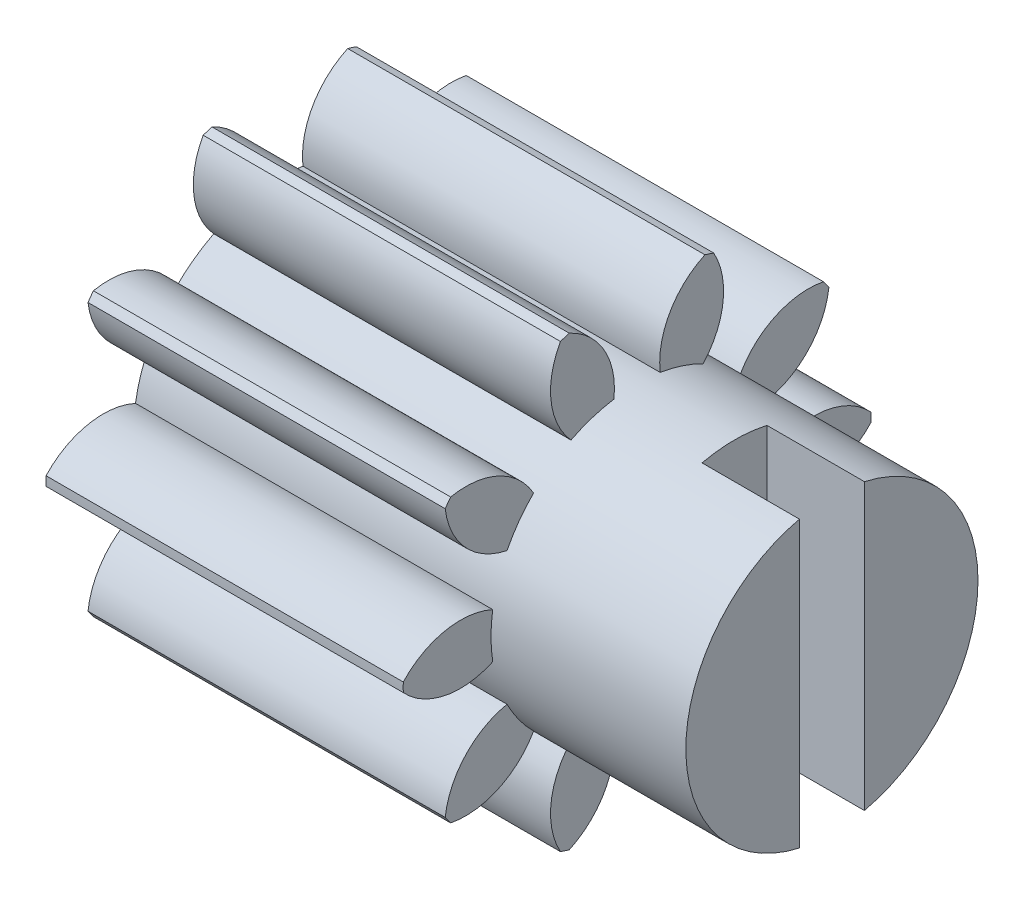
SolidWorks part; units mm, degrees
ref_plane "Plane1" through (0, 0, 0) normal (0, 0, 1) x (1, 0, 0)
ref_plane "Plane2" through (0, 0, 0) normal (0, 1, 0) x (1, 0, 0)
ref_plane "Plane3" through (0, 0, 0) normal (1, 0, 0) x (0, 0, -1)
other "Configuration Table"
sketch "HoldingSke" plane through (0, 0, 0) normal (0, 1, 0) x (1, 0, 0)
  line L0 (0, 0) -> (1.6413, -0.2894)
  line L1 (-15, 0) -> (100, 0) construction
  line L2 (0, 0) -> (-2.1039, 2.3779)
  line L3 (0, 0) -> (-11.863, 4.5341)
  line L4 (0, 0) -> (8.5048, 1.4996)
  line L5 (0, 0) -> (-46.8476, -17.4728)
  line L6 (0, 0) -> (-4.5593, -3.0762)
  line L7 (-2.1039, 2.3779) -> (8.6586, 51.2059)
  line L8 (-76.2, 54.61) -> (-76.1, 54.61)
  line L9 (-71.009, 38.7566) -> (-53.1078, 45.2721)
  line L10 (-76.2, 71.12) -> (104.1128, 71.12)
  line L11 (0, 0) -> (-5.5, 0)
  line L12 (-76.2, 101.6) -> (-76.177, 101.6)
  line L13 (24.9733, 27.94) -> (52.9518, 28.4284)
  line L14 (24.9733, 27.94) -> (24.9743, 27.94)
  line L15 (24.9733, 27.94) -> (100.4006, 29.5858)
  line L16 (-63.627, -0.6) -> (-12.827, -0.6)
  circle A0 centre (0, 0) radius 0.5
  circle A1 centre (0, 0) radius 2.249
  circle A2 centre (0, 0) radius 37.5
  circle A3 centre (0, 0) radius 0.5
  dimension "Num_teeth" = 10
  dimension "Pitch_radius" = 180.3128
  dimension "Width" = 5.5
  dimension "Thickness" = 5.5
sketch "BasProSke" plane through (0, 0, 0) normal (0, 1, 0) x (1, 0, 0)
  line L0 (-10, 0) -> (60, 0) construction
  line L1 (0, 0) -> (0, 3.6)
  line L2 (0, 0) -> (5.5, 0)
  line L3 (5.5, 0) -> (5.5, 3.6)
  line L4 (5.5, 3.6) -> (0, 3.6)
  dimension "Thickness" = 5.5
  dimension "Diameter" = 7.2
revolve "Base-Revolve" add sketch "BasProSke" angle 360 about L0
sketch "TooCutSke" plane through (0, 0, 0) normal (1, 0, 0) x (0, 0, -1)
  line L1 (0, 0) -> (0, 107) construction
  line L2 (0, 0) -> (-0.5095, 2.9564) construction
  line L3 (0, 0) -> (-1.835, 5.6477) construction
  line L4 (-0.5095, 2.9564) -> (-0.9175, 2.8238) construction
  arc A0 (0.356, 2.2206) -> (-0.356, 2.2206) centre (0, 0) ccw
  arc A1 (1.0802, 3.4607) -> (-1.0802, 3.4607) centre (0, 0) ccw
  circle A2 centre (0, 0) radius 3 construction
  circle A3 centre (0, 0) radius 2.8191 construction
  arc A4 (-0.356, 2.2206) -> (-1.0802, 3.4607) centre (-1.5483, 2.3558) ccw
  arc A5 (1.0802, 3.4607) -> (0.356, 2.2206) centre (1.5483, 2.3558) ccw
extrude "ToothCut" cut sketch "TooCutSke" along normal through all
fillet "Breaks" [suppressed] radius 0.012 tangent propagation no
fillet "RootFillets" [suppressed] radius 0.151
pattern_circular "TeethCuts" count 10 every 36 about axis through (-10, 0, 0) along (1, 0, 0) of "ToothCut", "RootFillets", "Breaks"
sketch "HubNeaOneSke" plane through (0, 0, 0) normal (-1, 0, 0) x (0, 0, 1)
  circle A0 centre (0, 0) radius 2.249
  dimension "Diameter" = 4.498
extrude "HubNearOne" [suppressed] add sketch "HubNeaOneSke" along normal blind 44.5001
sketch "HubNeaBotSke" plane through (0, 0, 0) normal (-1, 0, 0) x (0, 0, 1)
  circle A0 centre (0, 0) radius 2.249
  dimension "Diameter" = 4.498
extrude "HubNearBoth" [suppressed] add sketch "HubNeaBotSke" along normal blind 22.25
ref_plane "FarPln" through (5.5, 0, 0) normal (1, 0, 0) x (0, 0, -1)
sketch "HubFarSke" plane through (5.5, 0, 0) normal (1, 0, 0) x (0, 0, -1)
  circle A0 centre (0, 0) radius 2.249
  dimension "Diameter" = 4.498
extrude "HubFar" [suppressed] add sketch "HubFarSke" along normal blind 22.25
sketch "BorSke" plane through (0, 0, 0) normal (1, 0, 0) x (0, 0, -1)
  circle A0 centre (0, 0) radius 0.5
  dimension "Diameter" = 1
extrude "Bore" cut sketch "BorSke" along normal mid plane 100.0001
sketch "KeySke" plane through (0, 0, 0) normal (1, 0, 0) x (0, 0, -1)
  line L0 (-0.05, 0) -> (-0.05, 0.6)
  line L1 (-0.05, 0.6) -> (0.05, 0.6)
  line L2 (0.05, 0.6) -> (0.05, 0)
  line L3 (0, 0) -> (0, 34) construction
  line L4 (-0.05, 0) -> (0.05, 0)
  dimension "Width" = 0.1
extrude "Keyway" [suppressed] cut sketch "KeySke" along normal mid plane 100.0001
pattern_circular "Keyway2" [suppressed] count 2 every 90 about axis through (-10, 0, 0) along (1, 0, 0)
sketch "草图1" plane through (5.5, 0, 0) normal (1, 0, 0) x (0, 0, -1)
  circle A0 centre (0, 0) radius 0.5
  circle A1 centre (0, 0) radius 2.249
extrude "凸台-拉伸1" add sketch "草图1" along normal blind 3
sketch "草图2" plane through (8.5, 0, 0) normal (1, 0, 0) x (0, 0, -1)
  line L0 (-0.5, 0) -> (-0.5, -2.1927)
  line L1 (-0.5, 0) -> (-0.5, 2.1927)
  line L2 (0.5, 0) -> (0.5, 2.1927)
  line L3 (0.5, 0) -> (0.5, -2.1927)
  circle A0 centre (0, 0) radius 0.5 construction
  circle A1 centre (0, 0) radius 2.249 construction
  arc A2 (0.356, -2.2206) -> (1.0173, -2.0058) centre (0, 0) ccw construction
  arc A3 (-0.5, -2.1927) -> (0.5, -2.1927) centre (0, 0) ccw
  arc A5 (0.5, 2.1927) -> (-0.5, 2.1927) centre (0, 0) ccw
extrude "切除-拉伸1" cut sketch "草图2" against normal blind 1.5
equation "' \"Module@HoldingSke\" = 6.35"
equation "' \"Num_teeth@HoldingSke\" = 12"
equation "' \"Ap@HoldingSke\" =  20"
equation "' \"Ap@HoldingSke\" = 20"
equation "' \"Width@HoldingSke\" = 0.5 * 25.4"
equation "' \"Hub_dia@HoldingSke\"= 1 * 25.4"
equation "' \"Hub_dia@HoldingSke\" = 1 * 25.4"
equation "' \"Overall_len@HoldingSke\" = 1.0 * 25.4"
equation "' \"Bore@HoldingSke\" = 0.75 * 25.4"
equation "' \"T_dim@HoldingSke\" = 0.1 * 25.4"
equation "' \"Width@KeySke\" = 0.25 * 25.4"
equation "' \"Show_teeth@HoldingSke\" = 13"
equation "' \"Backlash@HoldingSke\" = 0.009 * 25.4"
equation "' \"Addendum_fac@HoldingSke\" = 1.0"
equation "' \"Dedendum_fac@HoldingSke\" = 1.25"
equation "' \"Dedendum_add@HoldingSke\" = 0.00005 * 25.4"
equation "' \"Clearance_fac@HoldingSke\" = 0.25"
equation "\"Pitch@HoldingSke\" = 1 / \"Module@HoldingSke\""
equation "\"Overcut_dia@TooCutSke\" = (\"Num_teeth@HoldingSke\" + 2 * \"Addendum_fac@HoldingSke\") / \"Pitch@HoldingSke\" + 0.002 * 25.4"
equation "\"Pitch_dia@TooCutSke\" = \"Num_teeth@HoldingSke\" / \"Pitch@HoldingSke\""
equation "\"Base_dia@TooCutSke\" = \"Num_teeth@HoldingSke\" / \"Pitch@HoldingSke\" * cos((\"Ap@HoldingSke\"  * 3.14159265 / 180))"
equation "\"Root_dia@TooCutSke\" = (\"Num_teeth@HoldingSke\" + 2) / \"Pitch@HoldingSke\" - 2 * (\"Addendum_fac@HoldingSke\" + \"Dedendum_fac@HoldingSke\") / \"Pitch@HoldingSke\" - \"Dedendum_add@HoldingSke\" * 2"
equation "\"Half_ang@TooCutSke\" = 180 / \"Num_teeth@HoldingSke\""
equation "\"Half_CT@TooCutSke\" = \"Num_teeth@HoldingSke\" / \"Pitch@HoldingSke\" * sin((3.14159265 / 2 / \"Num_teeth@HoldingSke\")) / 2 - 7 * \"Backlash@HoldingSke\" / 4"
equation "\"Flank_rad@TooCutSke\" = \"Num_teeth@HoldingSke\" / \"Pitch@HoldingSke\" / 5"
equation "\"Radius@RootFillets\" = \"Clearance_fac@HoldingSke\" / \"Pitch@HoldingSke\" + \"Dedendum_add@HoldingSke\""
equation "\"Break_rad@Breaks\" = 0.02 / \"Pitch@HoldingSke\""
equation "\"Thickness@HoldingSke\" = \"Width@HoldingSke\""
equation "\"OAL@HoldingSke\" = \"Thickness@HoldingSke\""
equation "\"MHD@HoldingSke\" = (\"Num_teeth@HoldingSke\" + 2) / \"Pitch@HoldingSke\" - 2 * (\"Addendum_fac@HoldingSke\" + \"Dedendum_fac@HoldingSke\")  / \"Pitch@HoldingSke\" - \"Dedendum_add@HoldingSke\" * 2"
equation "\"MBD@HoldingSke\" = (\"Num_teeth@HoldingSke\" + 2) / \"Pitch@HoldingSke\" - 2 * (\"Addendum_fac@HoldingSke\" + \"Dedendum_fac@HoldingSke\")  / \"Pitch@HoldingSke\" - \"Dedendum_add@HoldingSke\" * 2 - 0.002 * 25.4"
equation "\"MHD@HoldingSke\" = ((sgn( \"MHD@HoldingSke\" - \"Hub_dia@HoldingSke\" )-1)*( \"MHD@HoldingSke\" - \"Hub_dia@HoldingSke\" ))/-2+ \"Hub_dia@HoldingSke\""
equation "\"MBD@HoldingSke\" = ((sgn( \"MBD@HoldingSke\" - \"Bore@HoldingSke\" )-1)*( \"MBD@HoldingSke\" - \"Bore@HoldingSke\" ))/-2+ \"Bore@HoldingSke\""
equation "\"OAL@HoldingSke\" = ((sgn( \"OAL@HoldingSke\" - \"Overall_len@HoldingSke\" )+1)*( \"OAL@HoldingSke\" - \"Overall_len@HoldingSke\" ))/2 + \"Overall_len@HoldingSke\" + 0.000002 * 25.4"
equation "\"Num_teeth@TeethCuts\" = int( \"Show_teeth@HoldingSke\" ) + 1"
equation "\"Num_teeth@TeethCuts\" = ((sgn( \"Num_teeth@TeethCuts\" - \"Num_teeth@HoldingSke\" )-1)*( \"Num_teeth@TeethCuts\" - \"Num_teeth@HoldingSke\" ))/-2+ \"Num_teeth@HoldingSke\""
equation "\"Num_teeth@TeethCuts\" = ((sgn( \"Num_teeth@TeethCuts\" - 2.0)+1)*( \"Num_teeth@TeethCuts\" - 2.0))/2 +2.0"
equation "\"Angle@TeethCuts\" = 360.0 / \"Num_teeth@HoldingSke\""
equation "\"Diameter@BasProSke\" = (\"Num_teeth@HoldingSke\" + 2 * \"Addendum_fac@HoldingSke\") / \"Pitch@HoldingSke\""
equation "\"Thickness@BasProSke\"  = \"Thickness@HoldingSke\""
equation "' \"Fillet_rad@BasProSke\" =  \"Thickness@HoldingSke\" * 0.05"
equation "' \"Fillet_rad@BasProSke\" = \"Thickness@HoldingSke\" * 0.05"
equation "\"MHD@HoldingSke\" = ((sgn( \"MHD@HoldingSke\" - \"Root_dia@TooCutSke\" )-1)*( \"MHD@HoldingSke\" - \"Root_dia@TooCutSke\" ))/-2+ \"Root_dia@TooCutSke\""
equation "\"Diameter@HubNeaOneSke\" = \"MHD@HoldingSke\""
equation "\"Length@HubNearOne\" = \"OAL@HoldingSke\" - \"Thickness@BasProSke\""
equation "\"Diameter@HubNeaBotSke\" = \"MHD@HoldingSke\""
equation "\"Length@HubNearBoth\" = ( \"OAL@HoldingSke\" - \"Thickness@BasProSke\" ) / 2.0"
equation "\"Thickness@FarPln\" = \"Thickness@BasProSke\""
equation "\"Diameter@HubFarSke\" = \"MHD@HoldingSke\""
equation "\"Length@HubFar\" = ( \"OAL@HoldingSke\" - \"Thickness@BasProSke\" ) / 2.0"
equation "\"Diameter@BorSke\" = \"MBD@HoldingSke\""
equation "\"D1@Bore\" = \"OAL@HoldingSke\" * 2.0"
equation "\"D1@Keyway\" = \"OAL@HoldingSke\" * 2.0"
equation "\"Offset@KeySke\" = \"T_dim@HoldingSke\" + \"MBD@HoldingSke\" / 2.0"
